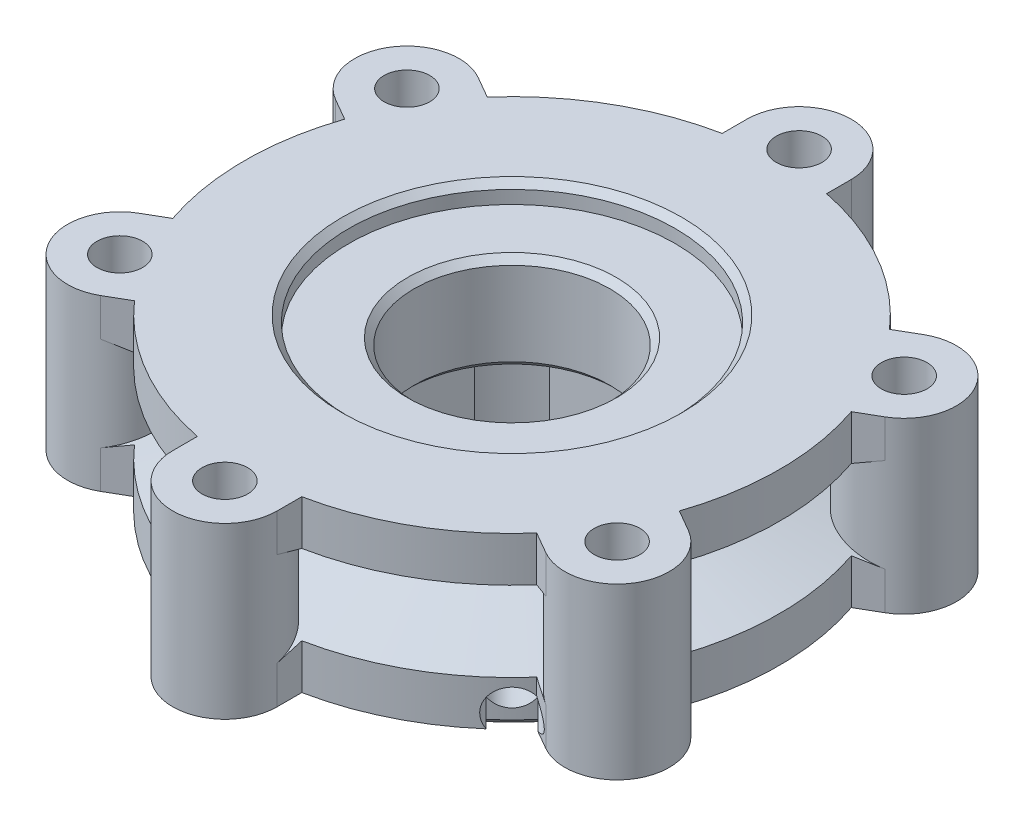
SolidWorks part; units mm, degrees
material "PLA/ABS"
ref_plane "Front Plane" through (0, 0, 0) normal (0, 0, 1) x (1, 0, 0)
ref_plane "Top Plane" through (0, 0, 0) normal (0, 1, 0) x (1, 0, 0)
ref_plane "Right Plane" through (0, 0, 0) normal (1, 0, 0) x (0, 0, -1)
other "Bounding Box"
ref_plane "Default Plane" through (13.8565, 3.175, 6.7999) normal (0, -1, 0) x (-1, 0, 0)
sketch "Sketch1" plane through (0, 0, 0) normal (0, 1, 0) x (1, 0, 0)
  line L0 (26.9408, -26.9408) -> (0, 0) construction
  line L1 (0, 0) -> (26.9408, 26.9408) construction
  line L2 (0, 0) -> (0, 38.1) construction
  circle A0 centre (0, 0) radius 38.1
  point P3 (0, 38.1)
  point P4 (38.1, 0)
  point P5 (-38.1, 0)
  point P6 (0, -38.1)
  point P7 (26.9408, 26.9408)
  point P8 (26.9408, -26.9408)
  dimension "D1" = 76.2
  dimension "D2" = 45
extrude "Boss-Extrude1" add sketch "Sketch1" along normal mid plane 16.51
ref_plane "Plane2" through (-38.1, 0, 0) normal (-1, 0, 0) x (0, 0, 1)
sketch "Sketch9" plane through (-38.1, 0, 0) normal (-1, 0, 0) x (0, 0, 1)
  line L0 (-0.635, -8.255) -> (0.635, -8.255)
  line L1 (-38.1, -8.255) -> (38.1, -8.255) construction
  line L2 (0.635, -8.255) -> (0.635, 0)
  line L3 (38.1, 8.255) -> (-38.1, 8.255) construction
  line L5 (-0.635, 0) -> (-0.635, -8.255)
  line L6 (0.635, -8.255) -> (0, -8.255) construction
  line L7 (0, -8.255) -> (0, 8.255) construction
  line L9 (-0.635, 0) -> (0.635, 0) construction
  line L10 (0.635, 0) -> (0.635, 8.255)
  line L11 (0.635, 8.255) -> (-0.635, 8.255)
  line L13 (-0.635, 8.255) -> (-0.635, 0)
  point P14 (0, 0)
  dimension "D2" = 1.27
extrude "Cut-Extrude4" cut sketch "Sketch9" against normal blind 0.635
sketch "Sketch4" plane through (0, 0, 0) normal (0, 0, 1) x (1, 0, 0)
  line L0 (-38.1, -8.255) -> (-35.56, -8.255)
  line L1 (-38.0947, -8.255) -> (38.1, -8.255) construction
  line L4 (38.1, 8.255) -> (-38.0947, 8.255) construction
  line L5 (-35.56, 8.255) -> (-38.1, 8.255)
  line L6 (-38.1, 8.255) -> (-38.1, -8.255)
  line L7 (-12.7, 0) -> (0, 0) construction
  line L8 (-35.56, -8.255) -> (-35.56, -6.6675)
  line L9 (-35.56, -6.6675) -> (-12.7, 0)
  line L10 (-12.7, 0) -> (-35.56, 6.6675)
  line L11 (-35.56, 6.6675) -> (-35.56, 8.255)
  point P17 (-38.1, 0)
  dimension "D1" = 2.54
  dimension "D2" = 25.4
  dimension "D3" = 1.5875
pattern_circular "CirPattern2" count 25 over 360 about axis through (0, -8.255, 0) along (0, 1, 0) of "Cut-Extrude4"
ref_axis "Axis1" through (0, -8.7312, 0) along (0, 1, 0)
sketch "Sketch3" plane through (0, 8.255, 0) normal (0, 1, 0) x (1, 0, 0)
  line L0 (0, 0) -> (0, 27.94) construction
  line L1 (0, 27.94) -> (0, 38.1) construction
  circle A0 centre (0, 27.94) radius 2.2225
  circle A1 centre (0, 0) radius 38.1 construction
  circle A2 centre (0, 27.94) radius 5.08
  dimension "D2" = 4.445
  dimension "D3" = 10.16
  dimension "D1" = 10.16
move or copy body "Body-Move/Copy1" [suppressed]
revolve "Cut-Revolve2" cut sketch "Sketch4" angle 360 about axis through (0, -8.7312, 0) along (0, 1, 0)
sketch "Sketch5" plane through (0, 8.255, 0) normal (0, 1, 0) x (1, 0, 0)
  circle A0 centre (0, 27.94) radius 5.08
  circle A1 centre (0, 27.94) radius 2.2225 construction
  circle A3 centre (0, 27.94) radius 2.2225
  circle A4 centre (0, 27.94) radius 5.08 construction
extrude "Boss-Extrude2" add sketch "Sketch5" against normal through all
sketch "Sketch12" plane through (0, 8.255, 0) normal (0, 1, 0) x (1, 0, 0)
  line L0 (-24.1967, 13.97) -> (0, 0) construction
  line L1 (-24.1967, -13.97) -> (-24.1967, 13.97) construction
  line L2 (-24.1967, 13.97) -> (0, 27.94) construction
  line L3 (-24.1967, -13.97) -> (0, 0) construction
  line L4 (0, 0) -> (0, 27.94) construction
  circle A0 centre (-24.1967, 13.97) radius 5.08
  circle A1 centre (0, 27.94) radius 5.08 construction
  dimension "D3" = 120
extrude "Boss-Extrude6" add sketch "Sketch12" against normal through all
sketch "Sketch17" plane through (0, 0, 0) normal (0, 1, 0) x (1, 0, 0)
  line L0 (0, 27.94) -> (0, 0) construction
  line L1 (0, 0) -> (-24.1967, 13.97) construction
  line L2 (0, 0) -> (-24.1967, -13.97) construction
  line L3 (-28.5962, -16.51) -> (-30.7959, -17.78)
  line L4 (0, 33.02) -> (0, 35.56)
  line L5 (-26.7367, -9.5706) -> (-24.6536, -8.3679)
  line L6 (-24.6536, 8.3679) -> (-26.7367, 9.5706)
  line L7 (-21.6567, 18.3694) -> (-19.5736, 17.1667)
  line L8 (-5.08, 27.94) -> (-5.08, 25.5346)
  circle A0 centre (0, 27.94) radius 5.08 construction
  circle A1 centre (-24.1967, 13.97) radius 5.08 construction
  arc A2 (0, 33.02) -> (-5.08, 27.94) centre (0, 27.94) ccw
  arc A3 (-21.6567, 18.3694) -> (-26.7367, 9.5706) centre (-24.1967, 13.97) ccw
  arc A5 (-5.08, 25.5346) -> (-19.5736, 17.1667) centre (0, 0) ccw
  circle A6 centre (0, 27.94) radius 2.2225 construction
  arc A7 (-26.7367, -9.5706) -> (-28.5962, -16.51) centre (-24.1967, -13.97) ccw
  circle A8 centre (0, 0) radius 35.56 construction
  circle A9 centre (0, 27.94) radius 2.2225
  circle A10 centre (0, 0) radius 35.56 construction
  arc A11 (0, 35.56) -> (-30.7959, -17.78) centre (0, 0) ccw
  arc A12 (-24.6536, 8.3679) -> (-24.6536, -8.3679) centre (0, 0) ccw
  circle A13 centre (-24.1967, 13.97) radius 2.2225
  circle A15 centre (-24.1967, -13.97) radius 2.2225
  dimension "D1" = 9.525
extrude "Cut-Extrude5" cut sketch "Sketch17" against normal through all both and the other way through all
pattern_circular "CirPattern1" count 3 over 360 about axis through (0, 6.6675, 0) along (0, -1, 0) of "Boss-Extrude2", "Boss-Extrude6", "Cut-Extrude5"
sketch "Sketch18" plane through (0, -8.255, 0) normal (0, -1, 0) x (1, 0, 0)
  circle A0 centre (0, 0) radius 26.035 construction
  circle A1 centre (0, 0) radius 16.51
  arc A2 (-5.08, 25.5346) -> (-19.5736, 17.1667) centre (0, 0) ccw construction
  circle A3 centre (0, 0) radius 12.7 construction
  circle A4 centre (0, 0) radius 12.7 construction
  dimension "D1" = 3.81
extrude "Boss-Extrude9" add sketch "Sketch18" against normal through all
fillet "Fillet5" radius 1.27 2 edges at (0, -1.1112, -16.51) (0, 1.1112, 16.51)
sketch "Sketch22" plane through (0, -8.255, 0) normal (0, -1, 0) x (1, 0, 0)
  circle A0 centre (0, 0) radius 22.225
  dimension "D1" = 44.45
extrude "Boss-Extrude12" add sketch "Sketch22" along normal blind 2.54
sketch "Sketch23" plane through (0, -10.795, 0) normal (0, -1, 0) x (1, 0, 0)
  line L0 (-8.5312, 8.5312) -> (-18.4095, 18.4095) construction
  line L1 (8.5312, 8.5312) -> (18.4095, 18.4095) construction
  arc A2 (24.6536, -8.3679) -> (24.6536, 8.3679) centre (0, 0) ccw construction
  arc A3 (-5.08, 25.5346) -> (-19.5736, 17.1667) centre (0, 0) ccw construction
  arc A4 (19.5736, 17.1667) -> (5.08, 25.5346) centre (0, 0) ccw construction
  line B0 (0, -10.16) -> (-6.5068, -10.16)
  line B1 (6.5068, -10.16) -> (0, -10.16)
  line B2 (10.16, 6.5068) -> (10.16, -6.5068)
  line B3 (0, 10.16) -> (6.5068, 10.16)
  line B4 (-6.5068, 10.16) -> (0, 10.16)
  line B5 (-10.16, -6.5068) -> (-10.16, 6.5068)
  arc B6 (-10.16, -6.5068) -> (-6.5068, -10.16) centre (0, 0) ccw
  arc B7 (6.5068, -10.16) -> (10.16, -6.5068) centre (0, 0) ccw
  arc B8 (10.16, 6.5068) -> (6.5068, 10.16) centre (0, 0) ccw
  arc B9 (-6.5068, 10.16) -> (-10.16, 6.5068) centre (0, 0) ccw
sketch_block_instance "Block-BaneBots Hub-1"
sketch_block "Block-BaneBots Hub"
extrude "Cut-Extrude6" cut sketch "Sketch23" against normal blind 7.747
sketch "Sketch24" plane through (0, -3.048, 0) normal (0, -1, 0) x (1, 0, 0)
  circle A0 centre (0, 0) radius 9.525
  dimension "D1" = 19.05
extrude "Cut-Extrude7" cut sketch "Sketch24" against normal through all
sketch "Sketch25" plane through (0, 8.255, 0) normal (0, 1, 0) x (1, 0, 0)
  circle A0 centre (0, 0) radius 15.875
  dimension "D1" = 31.75
extrude "Cut-Extrude8" cut sketch "Sketch25" against normal offset from surface (1.905 mm away) 17.145 up to face at (0, -10.795, 0)
ref_plane "Plane3" through (0, 0, 0) normal (0.7071, 0, -0.7071) x (-0.7071, 0, -0.7071)
sketch "Sketch33" plane through (0, 0, 0) normal (0.7071, 0, -0.7071) x (-0.7071, 0, -0.7071)
  line L0 (0, -3.048) -> (0, -10.795) construction
  line L1 (-2.5832, -10.795) -> (2.5832, -10.795) construction
  line L2 (-2.5832, -3.048) -> (2.5832, -3.048) construction
  circle A0 centre (0, -6.9215) radius 2.2225
  dimension "D1" = 4.445
extrude "Cut-Extrude9" cut sketch "Sketch33" along normal through all
ref_plane "Plane4" through (0, 0, 0) normal (0.7071, 0, 0.7071) x (0.7071, 0, -0.7071)
sketch "Sketch34" plane through (0, 0, 0) normal (0.7071, 0, 0.7071) x (0.7071, 0, -0.7071)
  line L0 (0, -3.048) -> (0, -10.795) construction
  line L1 (-2.5832, -10.795) -> (2.5832, -10.795) construction
  line L2 (-2.5832, -3.048) -> (2.5832, -3.048) construction
  circle A0 centre (0, -6.9215) radius 2.2225
  dimension "D1" = 4.445
extrude "Cut-Extrude10" cut sketch "Sketch34" along normal through all
sketch "Sketch37" plane through (0, 0, 0) normal (0.7071, 0, -0.7071) x (-0.7071, 0, -0.7071)
  circle A0 centre (0, -6.9215) radius 3.175
  circle A1 centre (0, -6.9215) radius 2.2225
  arc A2 (1.778, -8.255) -> (-1.7019, -5.4922) centre (0, -6.9215) ccw construction
  dimension "D1" = 6.35
extrude "Boss-Extrude19" [suppressed] add sketch "Sketch37" along normal up to vertex from offset 19.05
sketch "Sketch39" plane through (0, 0, 0) normal (0.7071, 0, 0.7071) x (0.7071, 0, -0.7071)
  circle A0 centre (0, -6.9215) radius 3.175
  circle A1 centre (0, -6.9215) radius 2.2225
  arc A2 (1.7019, -5.4922) -> (-1.778, -8.255) centre (0, -6.9215) ccw construction
  dimension "D1" = 6.35
extrude "Boss-Extrude20" [suppressed] add sketch "Sketch39" along normal up to vertex from offset 19.05
fillet "Fillet8" [suppressed] radius 0.635
chamfer "Chamfer5" distance 0.635 angle 45 12 edges at (0, -10.795, -22.225) (0, -10.795, -10.16) (8.5312, -10.795, -8.5312) (10.16, -10.795, 0) (8.5312, -10.795, 8.5312) (0, -10.795, 10.16) (-8.5312, -10.795, 8.5312) (-10.16, -10.795, 0) (-8.5312, -10.795, -8.5312) (0, 8.255, 15.875) (0, 6.35, -9.525) (0, -3.048, -9.525)
combine bodies "Combine3" [suppressed] bodies to combine 116 169
delete or keep bodies "Body-Delete/Keep 4" [suppressed] type keep bodies bodies 117
sketch "Sketch7" [suppressed] plane through (0, -8.255, 0) normal (0, -1, 0) x (1, 0, 0)
  circle A0 centre (0, 0) radius 44.45
  circle A1 centre (0, 0) radius 38.1 construction
  dimension "D1" = 6.35
extrude "Boss-Extrude4" [suppressed] add sketch "Sketch7" against normal offset from surface (19.685 mm away) 3.175 separate body offset beyond the face yes
combine bodies "Combine2" [suppressed] operation type add bodies to combine 110 114
sketch "Sketch15" [suppressed] plane through (0, 0, 0) normal (1, 0, 0) x (0, 0, -1)
  line L0 (-44.45, -8.255) -> (-49.53, -13.335)
  line L1 (-49.53, -13.335) -> (-43.18, -13.335)
  line L2 (-43.18, -13.335) -> (-38.1, -8.255)
  line L3 (-38.1, -8.255) -> (-44.45, -8.255)
  dimension "D1" = 5.08
  dimension "D2" = 45
ref_axis "Axis2" [suppressed] through (0, -11.7475, 0) along (0, 1, 0)
revolve "Revolve1" [suppressed] add sketch "Sketch15" angle 360 about axis through (0, -11.7475, 0) along (0, 1, 0)
fillet "Fillet4" [suppressed] radius 6.35
sketch "Sketch27" [suppressed] plane through (0, 11.43, 0) normal (0, 1, 0) x (1, 0, 0)
  line L0 (43.9941, 6.35) -> (50.8, 6.35)
  line L1 (50.8, -6.35) -> (43.9941, -6.35)
  line L2 (44.45, 0) -> (50.8, 0) construction
  circle A0 centre (50.8, 0) radius 1.905
  arc A1 (43.9941, -6.35) -> (43.9941, 6.35) centre (0, 0) ccw
  circle A2 centre (0, 0) radius 44.45 construction
  arc A3 (50.8, 6.35) -> (50.8, -6.35) centre (50.8, 0) cw
  dimension "D2" = 3.81
  dimension "D3" = 6.35
  dimension "D1" = 6.35
extrude "Boss-Extrude13" [suppressed] add sketch "Sketch27" against normal blind 9.525
pattern_circular "CirPattern7" [suppressed] count 3 over 360 of bodies 177
split "Split1" [suppressed] bodies to split 124
sketch "Sketch19" [suppressed] plane through (0, 11.43, 0) normal (0, 1, 0) x (1, 0, 0)
  line L0 (-23.622, 40.9145) -> (-22.352, 38.7148)
  line L1 (-23.622, -40.9145) -> (-22.352, -38.7148)
  line L2 (-47.244, 0) -> (0, 0) construction
  arc A0 (-22.352, 38.7148) -> (-22.352, -38.7148) centre (0, 0) ccw
  circle A1 centre (0, 0) radius 44.45 construction
  arc A2 (-23.622, 40.9145) -> (-23.622, -40.9145) centre (0, 0) ccw
  dimension "D2" = 2.54
  dimension "D3" = 0.254
  dimension "D1" = 120
extrude "Boss-Extrude10" [suppressed] add sketch "Sketch19" against normal blind 6.35 separate body
sketch "Sketch21" [suppressed] plane through (0, 11.43, 0) normal (0, 1, 0) x (1, 0, 0)
  line L0 (-22.352, 38.7148) -> (-22.225, 38.4948)
  line L1 (-22.352, -38.7148) -> (-22.225, -38.4948)
  line L2 (-22.352, 38.7148) -> (-23.622, 40.9145) construction
  line L3 (-23.622, -40.9145) -> (-22.352, -38.7148) construction
  arc A1 (-22.352, 38.7148) -> (-22.352, -38.7148) centre (0, 0) ccw construction
  arc A2 (-22.225, 38.4948) -> (-22.225, -38.4948) centre (0, 0) ccw
  arc A3 (-22.352, 38.7148) -> (-22.352, -38.7148) centre (0, 0) ccw
  circle A4 centre (0, 0) radius 44.45 construction
extrude "Boss-Extrude11" [suppressed] add sketch "Sketch21" against normal blind 3.1496
pattern_circular "CirPattern6" [suppressed] count 3 over 360 reverse direction yes of bodies 137 132
combine bodies "Combine4" [suppressed] bodies to combine 137 137 135 134
chamfer "Chamfer4" [suppressed] distance 0.635 angle 45
delete or keep bodies "Body-Delete/Keep 1" [suppressed] type delete bodies bodies 133
delete or keep bodies "Body-Delete/Keep 2" [suppressed] type delete bodies bodies 121
mirror "Mirror1" [suppressed] about plane through (0, 0, 0) normal (1, 0, 0) of bodies 121
delete or keep bodies "Body-Delete/Keep 3" [suppressed] type delete bodies bodies 121
sketch "Sketch28" [suppressed] plane through (0, 8.255, 0) normal (0, -1, 0) x (1, 0, 0)
  circle A0 centre (0, 0) radius 15.24
  dimension "D1" = 30.48
extrude "Boss-Extrude14" [suppressed] add sketch "Sketch28" along normal blind 0.635
sketch "Sketch29" [suppressed] plane through (0, 7.62, 0) normal (0, -1, 0) x (1, 0, 0)
  circle A0 centre (0, 0) radius 9.144
  dimension "D1" = 18.288
extrude "Boss-Extrude15" [suppressed] add sketch "Sketch29" along normal blind 10.16
sketch "Sketch30" [suppressed] plane through (0, -8.255, 0) normal (0, -1, 0) x (1, 0, 0)
  circle A12 centre (0, 0) radius 36.83
  circle A13 centre (0, 0) radius 34.29
  circle A14 centre (0, 0) radius 38.1 construction
  dimension "D1" = 1.27
  dimension "D2" = 2.54
extrude "Boss-Extrude16" [suppressed] add sketch "Sketch30" along normal blind 1.6002 separate body
sketch "Sketch31" [suppressed] plane through (0, -9.8552, 0) normal (0, -1, 0) x (1, 0, 0)
  line L0 (-5.9055, 27.94) -> (-5.9055, 36.3535)
  line L1 (-5.9055, 36.3535) -> (5.9055, 36.3535)
  line L2 (5.9055, 36.3535) -> (5.9055, 27.94)
  circle A1 centre (0, 27.94) radius 2.7305
  arc A2 (5.9055, 27.94) -> (-5.9055, 27.94) centre (0, 27.94) cw
  circle A3 centre (0, 27.94) radius 2.2225 construction
  circle A4 centre (0, 0) radius 36.83 construction
  dimension "D1" = 3.175
  dimension "D2" = 5.461
extrude "Boss-Extrude17" [suppressed] add sketch "Sketch31" against normal up to surface (1.6002 mm away)
fillet "Fillet6" [suppressed] radius 2.54
pattern_circular "CirPattern8" [suppressed] count 6 over 360 of bodies 182
sketch "Sketch32" [suppressed] plane through (0, -9.8552, 0) normal (0, -1, 0) x (1, 0, 0)
  line L0 (0, 0) -> (-2.7463, 39.2741) construction
  line L1 (2.7463, 39.2741) -> (0.7608, 36.8221)
  line L2 (0, 0) -> (0, 39.37) construction
  line L3 (-2.3026, 36.7579) -> (-2.7463, 39.2741)
  line L4 (-2.7463, 39.2741) -> (-0.7608, 36.8221)
  line L5 (-0.7608, 36.8221) -> (-2.3026, 36.7579)
  line L6 (2.3026, 36.7579) -> (2.7463, 39.2741)
  line L7 (0.7608, 36.8221) -> (2.3026, 36.7579)
  circle A0 centre (0, 0) radius 36.83 construction
  circle A1 centre (0, 0) radius 39.37 construction
  circle A2 centre (0, 0) radius 38.1 construction
  dimension "D2" = 1.27
  dimension "D1" = 6
  dimension "D3" = 35
  dimension "D4" = 4
extrude "Boss-Extrude18" [suppressed] add sketch "Sketch32" against normal up to surface (1.6002 mm away)
fillet "Fillet7" [suppressed] radius 0.635
pattern_circular "CirPattern9" [suppressed] count 10 over 360 of bodies 184
delete or keep bodies "Body-Delete/Keep 5" [suppressed] bodies 185
